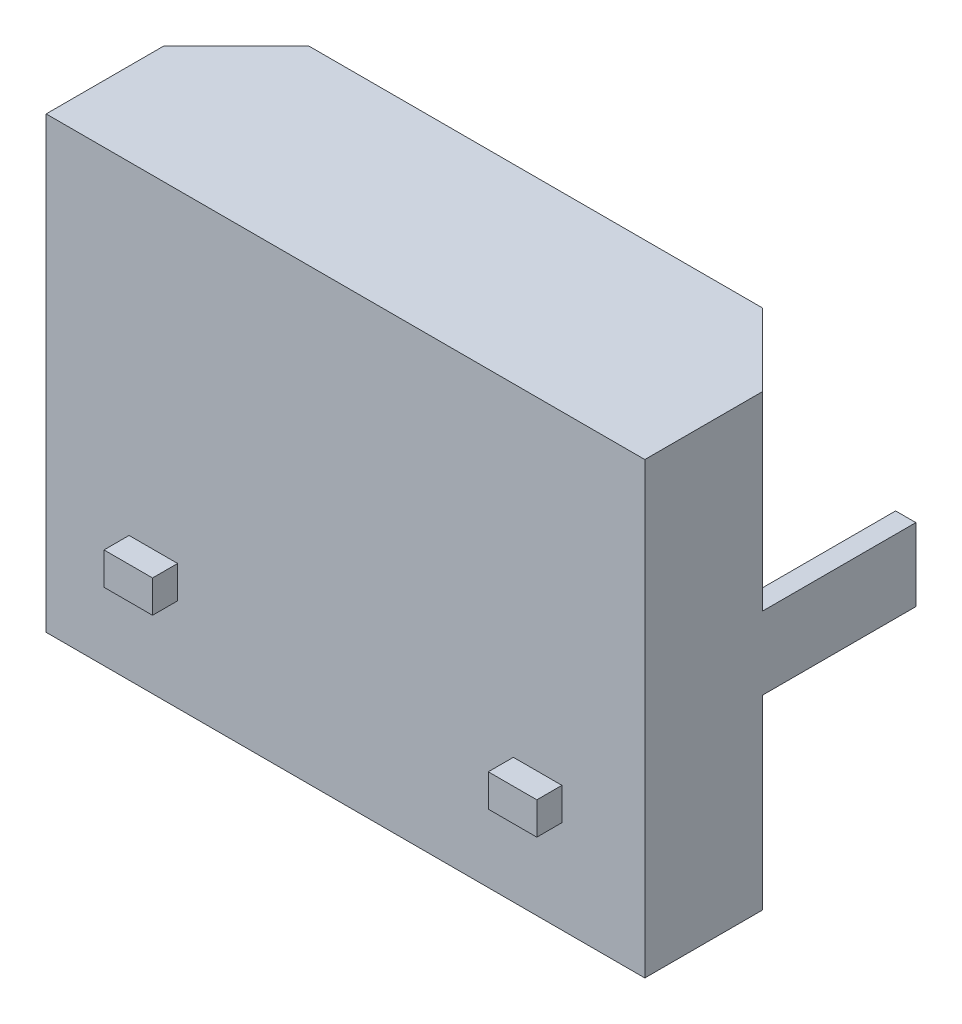
SolidWorks part; units mm, degrees
ref_plane "Front" through (0, 0, 0) normal (0, 0, 1) x (1, 0, 0)
ref_plane "Top" through (0, 0, 0) normal (0, 1, 0) x (1, 0, 0)
ref_plane "Right" through (0, 0, 0) normal (1, 0, 0) x (0, 0, -1)
sketch "Base sketch" plane through (0, 0, 0) normal (0, 0, 1) x (1, 0, 0)
  line L0 (-3.45, 2.1) -> (3.45, 2.1)
  line L1 (-3.45, 1) -> (-3.45, 2.1)
  line L2 (3.45, 1) -> (3.45, 2.1)
  line L3 (-3.7, 2.35) -> (-3.7, 0)
  line L4 (-3.45, 1) -> (-2.7, 0.25)
  line L5 (2.7, 0.25) -> (3.45, 1)
  line L6 (-2.7, 0.25) -> (2.7, 0.25)
  line L7 (-3.7, 0) -> (3.7, 0)
  line L8 (3.7, 0) -> (3.7, 2.35)
  line L9 (3.7, 2.35) -> (-3.7, 2.35)
  line L10 (-3.7, 0.8964) -> (-2.8036, 0)
  line L11 (2.8036, 0) -> (3.7, 0.8964)
  point P2 (0, 0.25)
  point P3 (0, 2.1)
  point P12 (0, 0)
  dimension "D1" = 1.85
  dimension "D2" = 6.9
  dimension "D3" = 1.1
  dimension "D4" = 7.4
  dimension "D5" = 5.4
  dimension "D6" = 2.35
  dimension "D7" = 0.25
  dimension "D8" = 0.25
  dimension "D9" = 0.25
  dimension "D10" = 0.25
extrude "Bulk" add sketch "Base sketch" along normal blind 2.75 and the other way blind 2.8 contours L7 L11 L8 L9 L3 L10 | L4 L6 L5 L2 L0 L1 region at (0, 1.2061, 0) region at (0, 2.2724, 0)
sketch "Peg base sketch" plane through (0, 2.35, 0) normal (0, 1, 0) x (1, 0, 0)
  line L0 (3.7, -0.45) -> (3.45, -0.45)
  line L1 (3.7, 2.8) -> (3.7, -2.75) construction
  line L2 (3.45, -0.45) -> (3.45, 0.45)
  line L3 (3.45, 0.45) -> (3.7, 0.45)
  line L4 (3.7, 0.45) -> (3.7, -0.45)
  line L5 (-3.7, -0.45) -> (-3.45, -0.45)
  line L6 (-3.7, 2.8) -> (-3.7, -2.75) construction
  line L7 (-3.45, -0.45) -> (-3.45, 0.45)
  line L8 (-3.45, 0.45) -> (-3.7, 0.45)
  line L9 (-3.7, 0.45) -> (-3.7, -0.45)
  point P12 (-3.7, 0)
  point P13 (3.7, 0)
  dimension "D1" = 0.9
  dimension "D2" = 0.25
extrude "Pegs" add sketch "Peg base sketch" against normal blind 3.35
extrude "Receptacle" cut sketch "Base sketch<3>" along normal through all and the other way blind 0.75 contours L4 L6 L5 L2 L0 L1 region at (0, 1.2061, 0)
sketch "Base sketch<3>" plane through (0, 0, 0) normal (0, 0, 1) x (1, 0, 0) same geometry as "Base sketch"
sketch "Sketch3" plane through (0, 2.35, 0) normal (0, 1, 0) x (1, 0, 0)
  line L0 (3.7, -2.75) -> (-3.7, -2.75) construction
  line L1 (-2.675, -1.6) -> (-2.075, -1.6)
  line L2 (-2.675, -1.6) -> (-2.675, -1.2)
  line L3 (-2.675, -1.2) -> (-2.075, -1.2)
  line L4 (-2.075, -1.6) -> (-2.075, -1.2)
  line L5 (2.075, -1.6) -> (2.675, -1.6)
  line L6 (2.075, -1.6) -> (2.075, -1.2)
  line L7 (2.075, -1.2) -> (2.675, -1.2)
  line L8 (2.675, -1.6) -> (2.675, -1.2)
  point P8 (2.375, -1.2)
  point P9 (2.075, -1.4)
  point P10 (-2.675, -1.4)
  point P11 (-2.375, -1.2)
  dimension "D1" = 1.35
  dimension "D2" = 0.4
  dimension "D3" = 2.375
  dimension "D4" = 0.6
  dimension "D5" = 2.375
extrude "Upper fins" add sketch "Sketch3" along normal blind 0.31
move or copy body "Altium axis align" bodies to move or copy 104 copy no rotation origin (0, 0, 0) rotation axis (1, 0, 0) rotation angle 90
